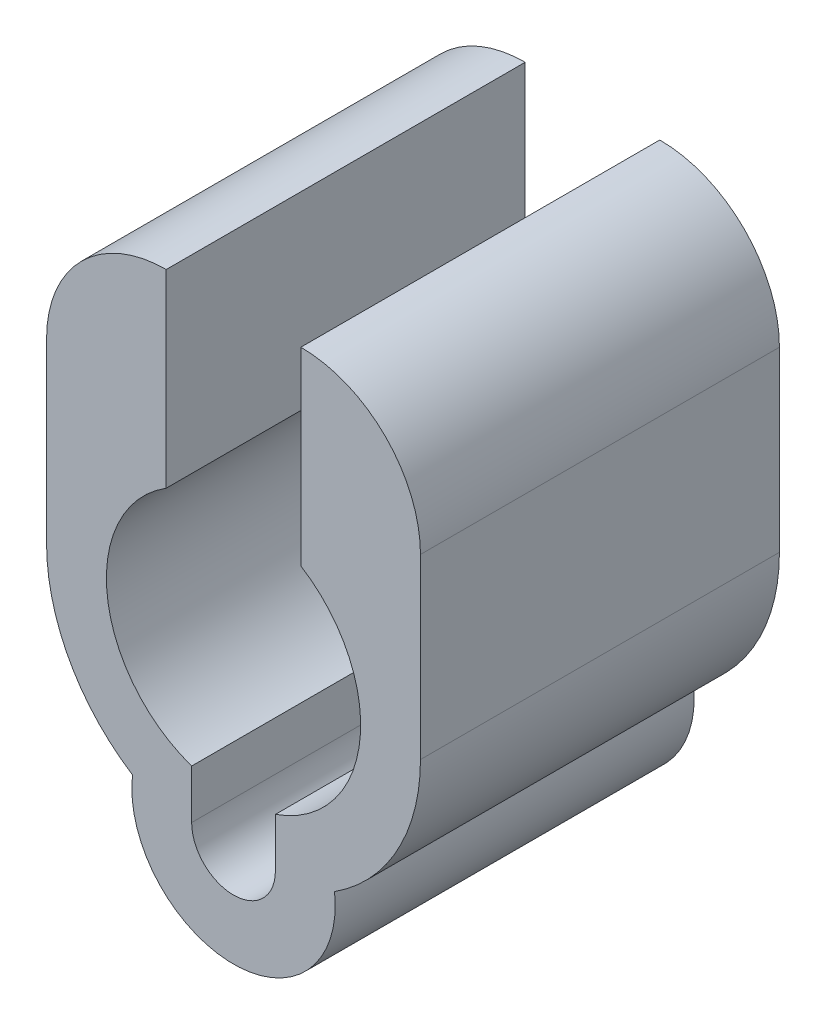
SolidWorks part; units mm, degrees
ref_plane "Ön Düzlem" through (0, 0, 0) normal (0, 0, 1) x (1, 0, 0)
ref_plane "Üst Düzlem" through (0, 0, 0) normal (0, 1, 0) x (1, 0, 0)
ref_plane "Sağ Düzlem" through (0, 0, 0) normal (1, 0, 0) x (0, 0, -1)
sketch "Sketch1" plane through (0, 0, 0) normal (0, 0, 1) x (1, 0, 0)
  line L0 (0, 0) -> (0, 5.5) construction
  line L1 (2.25, 3.6056) -> (2.25, 5.0187)
  line L2 (-2.25, 3.6056) -> (-2.25, 5.0187)
  line L3 (-2.25, 0) -> (-2.25, 8.1938) construction
  line L4 (0, 0) -> (0, 8.1938) construction
  line L5 (2.25, 0) -> (2.25, 8.1938) construction
  line L6 (-2.25, 9.9372) -> (2.25, 9.9372)
  line L7 (-1.4, -5.65) -> (-1.4, -4.0128)
  line L8 (1.4, -5.65) -> (1.4, -4.0128)
  line L9 (-2.25, 5.0187) -> (-2.25, 9.9372)
  line L10 (2.25, 5.0187) -> (2.25, 9.9372)
  line L13 (-6.25, 0) -> (-6.25, 5.9372)
  line L19 (6.25, 0) -> (6.25, 5.9372)
  arc A0 (3.3774, -5.2588) -> (6.25, 0) centre (0, 0) ccw
  arc A1 (-1.4, -5.65) -> (1.4, -5.65) centre (0, -5.65) ccw
  arc A2 (-3.3774, -5.2588) -> (3.3774, -5.2588) centre (0, -5.65) ccw
  circle A3 centre (0, -5.65) radius 3.4 construction
  circle A4 centre (0, 0) radius 6.25 construction
  circle A5 centre (0, 0) radius 4.25 construction
  circle A6 centre (0, -5.65) radius 1.4 construction
  arc A7 (-6.25, 0) -> (-3.3774, -5.2588) centre (0, 0) ccw
  arc A8 (6.25, 5.9372) -> (2.25, 9.9372) centre (2.25, 5.9372) ccw
  arc A9 (-6.25, 5.9372) -> (-2.25, 9.9372) centre (-2.25, 5.9372) cw
  arc A11 (1.4, -4.0128) -> (-1.4, -4.0128) centre (0, 0) ccw
  dimension "D1" = 2
  dimension "D2" = 2
  dimension "D5" = 4.25
  dimension "D6" = 4
  dimension "D3" = 2.25
  dimension "D4" = 2.25
extrude "Boss-Extrude1" add sketch "Sketch1" along normal blind 10 contours A11 L10 L1 A0 L2 L9 | L10 | L9 region at (2.4773, 4.3121, 0)
extrude "Boss-Extrude2" add sketch "Sketch1<5>" against normal blind 2 contours L10 | L9 region at (2.4773, 4.3121, 0)
sketch "Sketch1<5>" plane through (0, 0, 0) normal (0, 0, 1) x (1, 0, 0) same geometry as "Sketch1"
